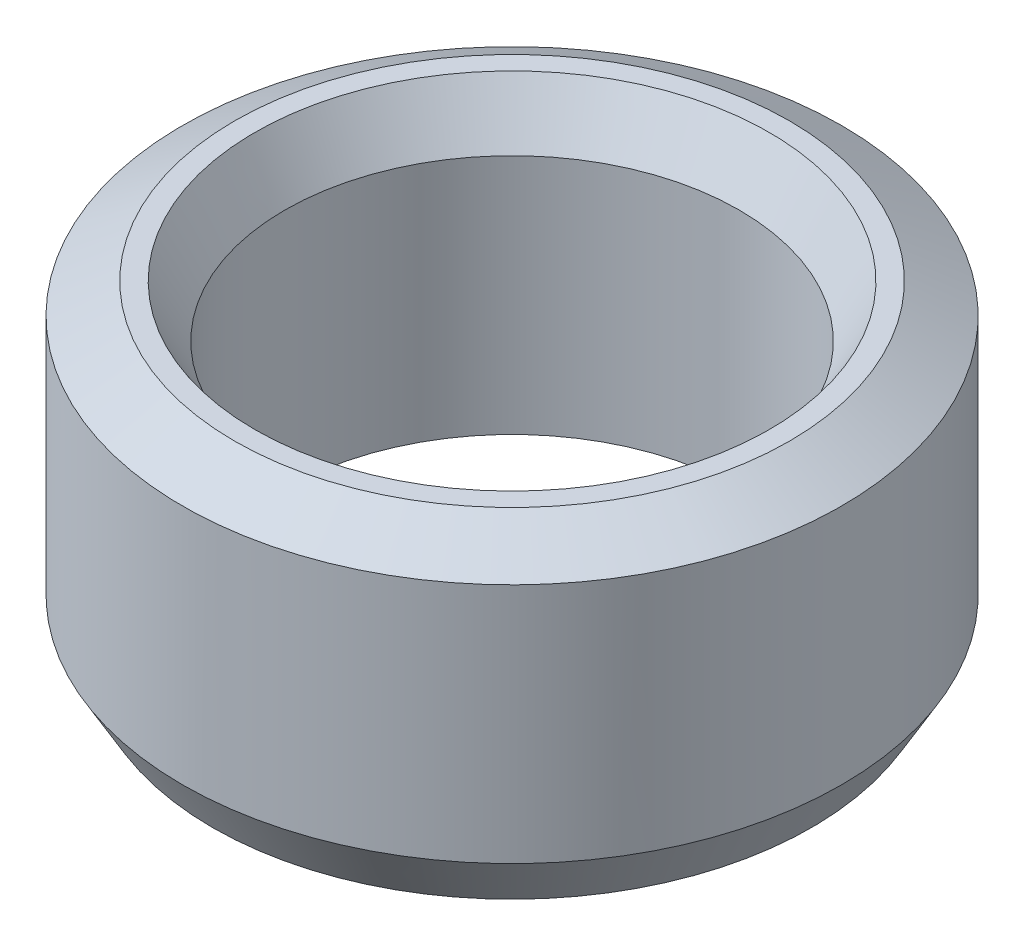
SolidWorks part; units mm, degrees
ref_plane "Front Plane" through (0, 0, 0) normal (0, 0, 1) x (1, 0, 0)
ref_plane "Top Plane" through (0, 0, 0) normal (0, 1, 0) x (1, 0, 0)
ref_plane "Right Plane" through (0, 0, 0) normal (1, 0, 0) x (0, 0, -1)
sketch "Sketch1" plane through (0, 0, 0) normal (0, 1, 0) x (1, 0, 0)
  circle A0 centre (0, 0) radius 7.5
  dimension "SLEEVE_OD" = 15
extrude "Boss-Extrude1" add sketch "Sketch1" along normal blind 7.3658
sketch "Sketch2" plane through (0, 0, 0) normal (0, 1, 0) x (1, 0, 0)
  circle A0 centre (0, 0) radius 5.1706
  dimension "BORE_D" = 10.3412
extrude "Cut-Extrude1" cut sketch "Sketch2" along normal through all
chamfer "Chamfer1" distance 0.6851 angle 60 4 edges at (0, 7.3658, 5.1706) (0, 0, 5.1706) (0, 0, 7.5) (0, 7.3658, 7.5) first distance on face at (0, 7.3658, 5.1706) first distance on face at (0, 0, 5.1706) first distance on face at (0, 7.3658, 7.5)
